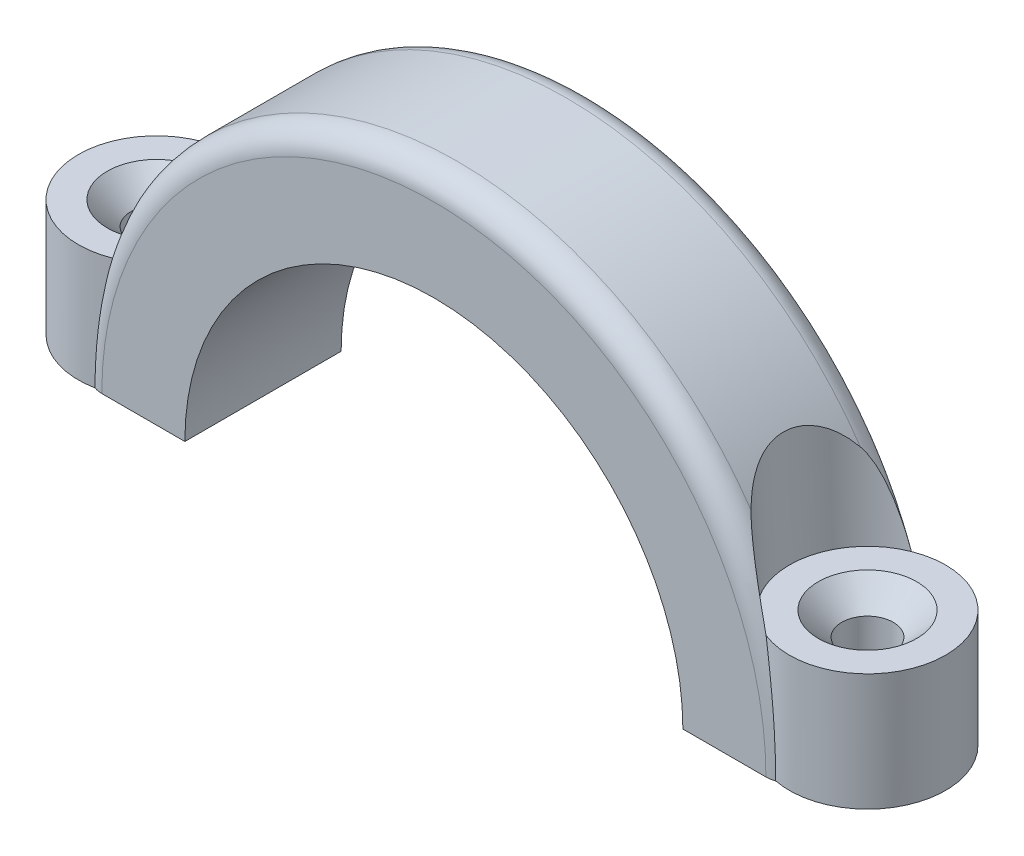
SolidWorks part; units mm, degrees
material "AISI 4340 Steel, normalized"
ref_plane "Front Plane" through (0, 0, 0) normal (0, 0, 1) x (1, 0, 0)
ref_plane "Top Plane" through (0, 0, 0) normal (0, 1, 0) x (1, 0, 0)
ref_plane "Right Plane" through (0, 0, 0) normal (1, 0, 0) x (0, 0, -1)
sketch "Sketch1" plane through (0, 0, 0) normal (0, 0, 1) x (1, 0, 0)
  line L0 (-45.5, 0) -> (-31.87, 0)
  line L1 (31.87, 0) -> (45.5, 0)
  arc A0 (-45.5, 0) -> (45.5, 0) centre (0, 0) cw
  arc A1 (-31.87, 0) -> (31.87, 0) centre (0, 0) cw
  dimension "D1" = 31.87
  dimension "D2" = 45.5
extrude "Boss-Extrude1" add sketch "Sketch1" along normal mid plane 20
sketch "Sketch2" plane through (0, 0, 0) normal (0, -1, 0) x (1, 0, 0)
  line L0 (-45.5, 10) -> (-45.5, -10) construction
  circle A0 centre (-45.5, 0) radius 10
  dimension "D1" = 20
extrude "Boss-Extrude2" add sketch "Sketch2" against normal blind 15
extrude "Cut-Extrude1" cut sketch "Sketch2<2>" against normal blind 45 draft 3 from offset 15 draft outward yes offset against normal yes
sketch "Sketch2<2>" plane through (0, 0, 0) normal (0, -1, 0) x (1, 0, 0) same geometry as "Sketch2"
hole_wizard "CSK for M6 Flat Head Machine Screw1" positions "Sketch3" profile "Sketch4" countersink size "M6" standard "ANSI Metric" end condition through all
sketch "Sketch3" plane through (0, 15, 0) normal (0, 1, 0) x (1, 0, 0)
  point P0 (-45.5, 0)
sketch "Sketch4" plane through (-45.5, 15, 0) normal (1, 0, 0) x (0, 0, 1)
  line L0 (0, 0) -> (0, 15)
  line L1 (0, 15) -> (3.3, 15)
  line L2 (3.3, 15) -> (3.3, 3)
  line L3 (3.3, 3) -> (6.3, 0)
  line L5 (6.3, 0) -> (0, 0)
  line L6 (-3.3, 3) -> (-6.3, 0) construction
  line L11 (0, -6.35) -> (0, 107.95) construction
  dimension "Thru Hole Dia." = 6.6
  dimension "Thru Hole Depth" = 15
  dimension "Near C'Sink Dia." = 12.6
  dimension "Near C'Sink Angle" = 90
mirror "Mirror1" about plane through (0, 0, 0) normal (1, 0, 0) of "Boss-Extrude2", "CSK for M6 Flat Head Machine Screw1", "Cut-Extrude1"
fillet "Fillet1" radius 3 2 edges at (0, 45.5, 10) (0, 45.5, -10)
